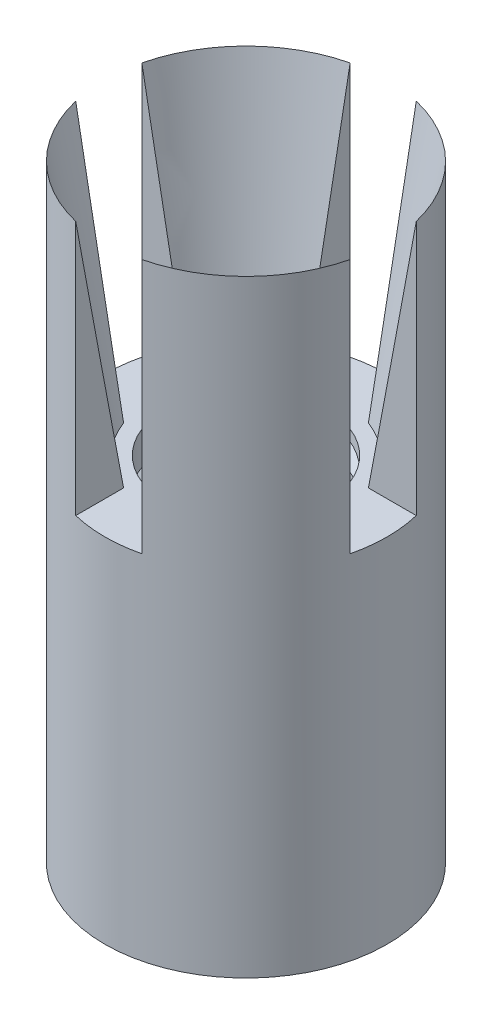
SolidWorks part; units mm, degrees
ref_plane "Front Plane" through (0, 0, 0) normal (0, 0, 1) x (1, 0, 0)
ref_plane "Top Plane" through (0, 0, 0) normal (0, 1, 0) x (1, 0, 0)
ref_plane "Right Plane" through (0, 0, 0) normal (1, 0, 0) x (0, 0, -1)
sketch "Sketch1" plane through (0, 0, 0) normal (0, 1, 0) x (1, 0, 0)
  circle A0 centre (0, 0) radius 2.8956
  circle A1 centre (0, 0) radius 5.08
  dimension "D1" = 5.7912
  dimension "D2" = 10.16
extrude "Boss-Extrude1" add sketch "Sketch1" along normal blind 12.7 contours A1 A0 region at (-4.9363, 0, 0)
sketch "Sketch2" plane through (0, 12.7, 0) normal (0, 1, 0) x (1, 0, 0)
  circle A0 centre (0, 0) radius 5.08
  dimension "D1" = 10.16
extrude "Boss-Extrude2" add sketch "Sketch2" along normal blind 12.7
ref_plane "Plane1" through (0, 12.7, 0) normal (0, 1, 0) x (1, 0, 0)
ref_axis "Axis1" through (0, 25.4, 0) along (0, -1, 0)
sketch "Sketch6" plane through (0, 0, 0) normal (0, 0, 1) x (1, 0, 0)
  line L0 (-5.08, 25.4) -> (5.08, 25.4) construction
  line L1 (0, 25.4) -> (-5.715, 25.4)
  line L2 (-5.715, 25.4) -> (-3.1775, 12.7)
  line L3 (6.2865, 12.7) -> (-6.2865, 12.7) construction
  line L4 (-3.1775, 12.7) -> (-5.715, 12.7)
  line L5 (-5.715, 12.7) -> (-5.715, 25.4)
  line L6 (0, 25.4) -> (0, 0) construction
  dimension "D1" = 3.1775
  dimension "D2" = 5.715
extrude "Cut-Extrude2" cut sketch "Sketch6" against normal mid plane 2.3812 contours L5 L4 L2 region at (-4.8692, 16.9333, 0)
sketch "Sketch3" plane through (0, 12.7, 0) normal (0, 1, 0) x (1, 0, 0)
  circle A0 centre (0, 0) radius 3.429
  dimension "D1" = 6.858
sketch "Sketch4" plane through (0, 25.4, 0) normal (0, 1, 0) x (1, 0, 0)
  circle A0 centre (0, 0) radius 5.715
  dimension "D1" = 11.43
loft "Cut-Loft2" cut profiles "Sketch3", "Sketch4" connector at (0, 12.7, 3.429) connector at (0, 25.4, 5.715)
sketch "Sketch8" plane through (0, 0, 0) normal (1, 0, 0) x (0, 0, -1)
  line L0 (0, 0) -> (0, 24.7529) construction
  line L1 (0, 25.4) -> (0, 0) construction
  line L2 (5.588, 12.7) -> (-5.588, 12.7) construction
  line L3 (-1.1906, 12.7) -> (1.1906, 12.7)
  line L4 (-1.1906, 12.7) -> (-1.1906, 23.7829)
  line L5 (-1.1906, 23.7829) -> (1.1906, 23.7829)
  line L6 (1.1906, 12.7) -> (1.1906, 23.7829)
  line L7 (-1.1906, 12.7) -> (1.1906, 23.7829) construction
  line L8 (-1.1906, 23.7829) -> (1.1906, 12.7) construction
  point P9 (0, 18.2415)
  point P12 (0, 23.7829)
  dimension "D1" = 2.3812
extrude "Cut-Extrude4" cut sketch "Sketch8" against normal through all both and the other way through all
sketch "Sketch9" plane through (0, 0, 0) normal (0, 0, 1) x (1, 0, 0)
  line L0 (0, 0) -> (0, 25.1481) construction
  line L1 (0, 25.4) -> (0, 0) construction
  line L2 (5.588, 12.7) -> (-5.588, 12.7) construction
  line L3 (-1.1906, 12.7) -> (1.1906, 12.7)
  line L4 (-1.1906, 12.7) -> (-1.1906, 24.1062)
  line L5 (-1.1906, 24.1062) -> (1.1906, 24.1062)
  line L6 (1.1906, 12.7) -> (1.1906, 24.1062)
  line L7 (-1.1906, 12.7) -> (1.1906, 24.1062) construction
  line L8 (-1.1906, 24.1062) -> (1.1906, 12.7) construction
  point P9 (0, 18.4031)
  point P12 (0, 24.1062)
  dimension "D1" = 2.3812
extrude "Cut-Extrude5" cut sketch "Sketch9" against normal through all both and the other way through all
thread "Thread1" pitch 1.27 method cut profile "Thread Profile1" start angle 0, offset 0, length 0, pitch 1.27, diameter 5.7912
ref_plane "Plane2" through (-2.8956, 12.7, 0) normal (0, 0, 1) x (-1, 0, 0)
sketch "Thread Profile1" plane through (-2.8956, 12.7, 0) normal (0, 0, 1) x (-1, 0, 0)
  line L0 (0, 0) -> (0, 1.27) construction
  line L1 (0, 0) -> (0.6874, 0.3969)
  line L2 (0.6874, 0.3969) -> (0.6874, 0.5556)
  line L3 (0.6874, 0.5556) -> (0, 0.9525)
  line L4 (0.6874, 0.4762) -> (0, 0.4762) construction
  line L11 (0, 0) -> (0, 0.9525)
  point P2 (0, 0)
  dimension "Pitch" = 1.27
  dimension "Profile_Angle" = 60
  dimension "Profile_Land" = 0.1588
  dimension "Profile_Height" = 0.6874
